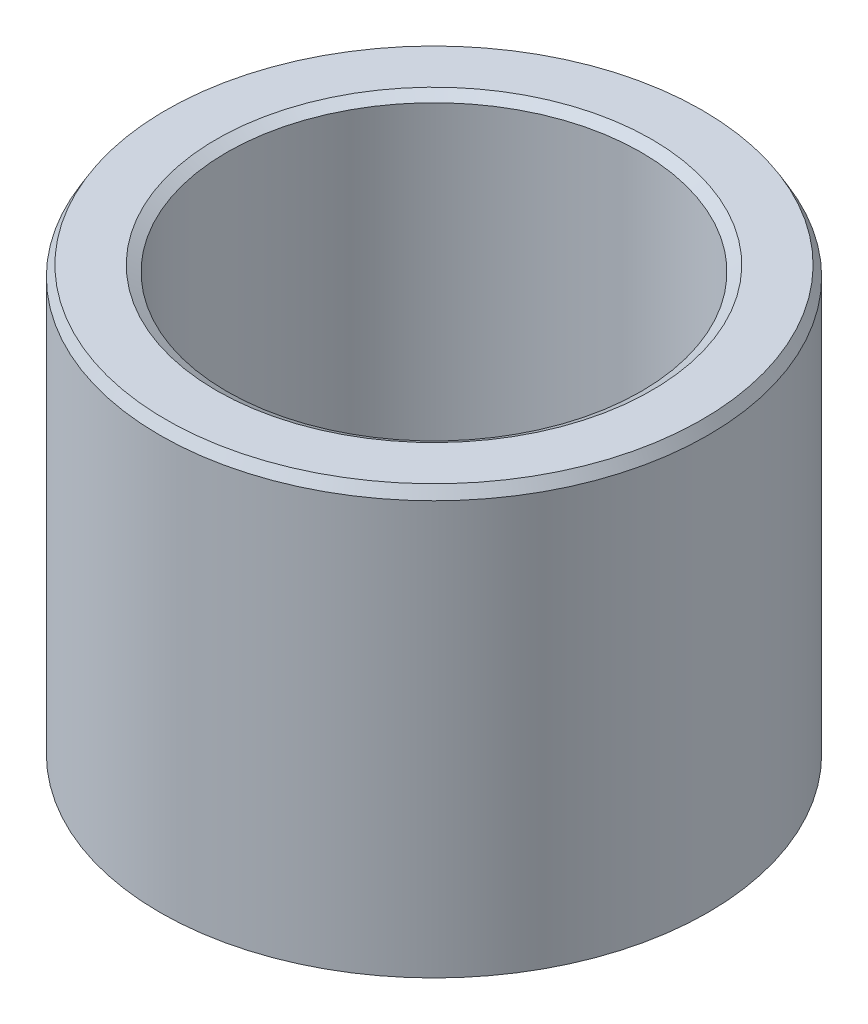
SolidWorks part; units mm, degrees
ref_plane "Front Plane" through (0, 0, 0) normal (0, 0, 1) x (1, 0, 0)
ref_plane "Top Plane" through (0, 0, 0) normal (0, 1, 0) x (1, 0, 0)
ref_plane "Right Plane" through (0, 0, 0) normal (1, 0, 0) x (0, 0, -1)
sketch "Sketch1" plane through (0, 0, 0) normal (0, 1, 0) x (1, 0, 0)
  circle A0 centre (0, 0) radius 40
  dimension "SLEEVE_OD" = 80
extrude "Boss-Extrude1" add sketch "Sketch1" along normal blind 62.7172
sketch "Sketch2" plane through (0, 0, 0) normal (0, 1, 0) x (1, 0, 0)
  circle A0 centre (0, 0) radius 30.2274
  dimension "BORE_D" = 60.4549
extrude "Cut-Extrude1" cut sketch "Sketch2" along normal through all
chamfer "Chamfer1" distance 1.5291 angle 30 4 edges at (0, 62.7172, 30.2274) (0, 0, 30.2274) (0, 0, 40) (0, 62.7172, 40) first distance on face at (0, 62.7172, 30.2274) first distance on face at (0, 0, 30.2274) first distance on face at (0, 62.7172, 40)
